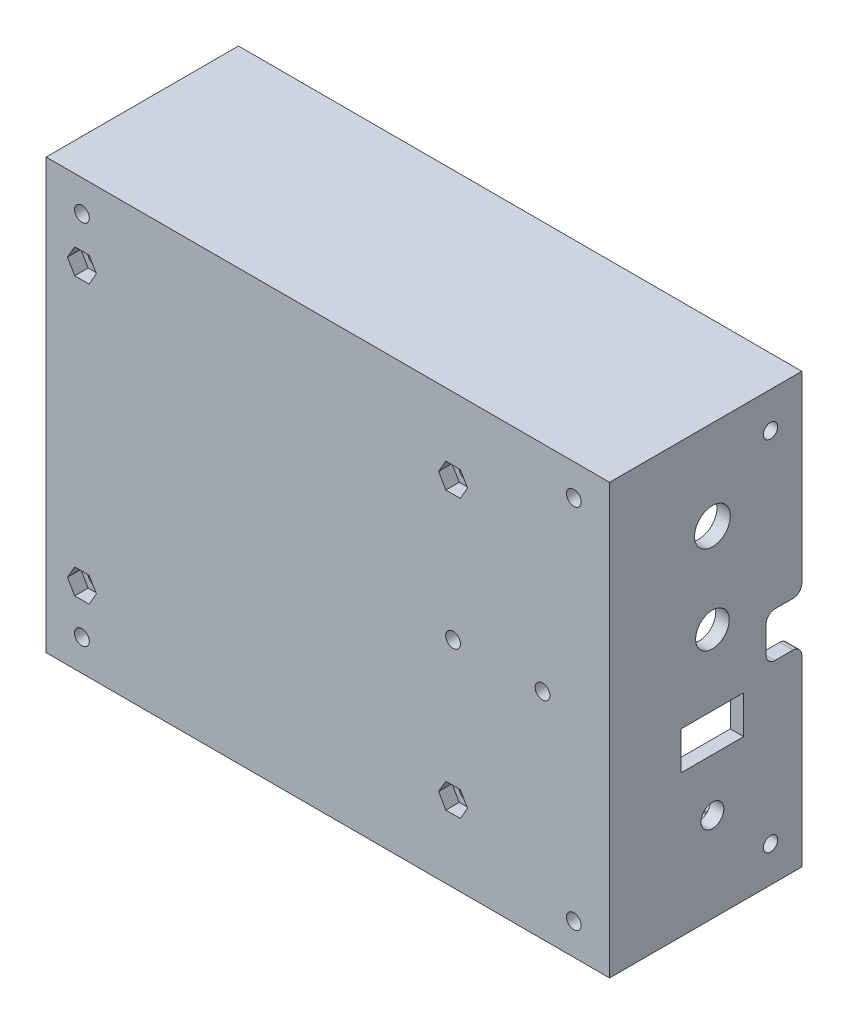
SolidWorks part; units mm, degrees
ref_plane "Front Plane" through (0, 0, 0) normal (0, 0, 1) x (1, 0, 0)
ref_plane "Top Plane" through (0, 0, 0) normal (0, 1, 0) x (1, 0, 0)
ref_plane "Right Plane" through (0, 0, 0) normal (1, 0, 0) x (0, 0, -1)
sketch "Sketch1" plane through (0, 0, 0) normal (0, 0, 1) x (1, 0, 0)
  line L1 (-60, -45) -> (60, -45)
  line L2 (-60, -45) -> (-60, 45)
  line L3 (-60, 45) -> (60, 45)
  line L4 (60, -45) -> (60, 45)
  line L5 (-60, -45) -> (60, 45) construction
  line L6 (-60, 45) -> (60, -45) construction
  line L7 (-55, -31) -> (28, -31)
  line L8 (-55, -31) -> (-55, 31)
  line L9 (-55, 31) -> (28, 31)
  line L10 (28, -31) -> (28, 31)
  line L11 (-55, -31) -> (28, 31) construction
  line L12 (-55, 31) -> (28, -31) construction
  circle A0 centre (-55, 31) radius 1.65
  circle A1 centre (28, 31) radius 1.65
  circle A2 centre (28, -31) radius 1.65
  circle A3 centre (-55, -31) radius 1.65
  circle A4 centre (-55, 41) radius 1.65
  circle A5 centre (55, 41) radius 1.65
  circle A6 centre (55, -41) radius 1.65
  circle A7 centre (-55, -41) radius 1.65
  point P0 (0, 0)
  point P6 (-13.5, 0)
  dimension "D7" = 3.3
  dimension "D8" = 4
  dimension "D9" = 5
  dimension "D10" = 5
  dimension "D11" = 4
  dimension "D12" = 3.3
  dimension "D13" = 5
  dimension "D14" = 4
  dimension "D15" = 4
  dimension "D16" = 5
  dimension "D1" = 90
  dimension "D2" = 120
  dimension "D3" = 62
  dimension "D4" = 83
  dimension "D5" = 14
  dimension "D6" = 5
extrude "Boss-Extrude2" add sketch "Sketch1" along normal blind 4 contours L1 L4 L3 L2 A3 L8 A0 L9 A1 L10 A2 L7 | A3 L7 A2 L10 A1 L9 A0 L8 region at (-58.5, 0, 0) region at (-13.5, 0, 0)
sketch "Sketch2" plane through (0, 0, 4) normal (0, 0, 1) x (1, 0, 0)
  line L1 (60, -45) -> (-60, -45)
  line L2 (60, -45) -> (60, 45)
  line L3 (60, 45) -> (-60, 45)
  line L4 (-60, -45) -> (-60, 45)
  line L5 (60, -45) -> (-60, 45) construction
  line L6 (60, 45) -> (-60, -45) construction
  line L7 (63, -48) -> (-63, -48)
  line L8 (63, -48) -> (63, 48)
  line L9 (63, 48) -> (-63, 48)
  line L10 (-63, -48) -> (-63, 48)
  line L11 (63, -48) -> (-63, 48) construction
  line L12 (63, 48) -> (-63, -48) construction
  point P0 (0, 0)
  point P7 (0, 0)
  dimension "D1" = 3
  dimension "D2" = 3
extrude "Boss-Extrude3" add sketch "Sketch2" against normal blind 43
sketch "Sketch3" plane through (-63, 0, 0) normal (-1, 0, 0) x (0, 0, 1)
  line L0 (-39, 48) -> (-39, -48) construction
  line L1 (-39, 48) -> (4, 48) construction
  line L2 (-39, -48) -> (4, -48) construction
  circle A0 centre (-32, -40) radius 1.6
  circle A1 centre (-32, 40) radius 1.6
  dimension "D1" = 3.2
  dimension "D2" = 7
  dimension "D3" = 8
  dimension "D4" = 8
  dimension "D5" = 7
  dimension "D6" = 3.2
extrude "Cut-Extrude1" cut sketch "Sketch3" against normal up to surface (126 mm away) up to face at (63, 0, -17.5)
sketch "Sketch4" plane through (63, 0, 0) normal (1, 0, 0) x (0, 0, -1)
  line L0 (39, -48) -> (39, 48) construction
  line L1 (39, 5) -> (31, 5)
  line L2 (39, 5) -> (39, -5)
  line L3 (39, -5) -> (31, -5)
  line L4 (31, 5) -> (31, -5)
  line L5 (39, -48) -> (-4, -48) construction
  line L6 (39, 48) -> (-4, 48) construction
  line L9 (12, -16.25) -> (26, -16.25)
  line L10 (12, -16.25) -> (12, -7.75)
  line L11 (12, -7.75) -> (26, -7.75)
  line L12 (26, -16.25) -> (26, -7.75)
  line L13 (12, -16.25) -> (26, -7.75) construction
  line L14 (12, -7.75) -> (26, -16.25) construction
  circle A1 centre (19, 8) radius 3.75
  point P8 (19, -12)
  dimension "D4" = 7.5
  dimension "D5" = 8.5
  dimension "D6" = 20
  dimension "D7" = 14
  dimension "D8" = 40
  dimension "D9" = 20
  dimension "D1" = 8
  dimension "D2" = 10
  dimension "D3" = 43
  dimension "D10" = 20
extrude "Cut-Extrude3" cut sketch "Sketch4" against normal blind 10
sketch "Sketch5" plane through (63, 0, 0) normal (1, 0, 0) x (0, 0, -1)
  line L0 (39, 5) -> (39, 48) construction
  line L1 (39, 48) -> (-4, 48) construction
  circle A0 centre (19, 28) radius 4
  dimension "D1" = 8
  dimension "D2" = 20
  dimension "D3" = 20
extrude "Cut-Extrude4" cut sketch "Sketch5" against normal blind 10
sketch "Sketch6" plane through (63, 0, 0) normal (1, 0, 0) x (0, 0, -1)
  line L0 (27, -28) -> (11, -28)
  line L1 (39, -48) -> (39, -5) construction
  line L3 (39, -48) -> (-4, -48) construction
  line L4 (-4, -48) -> (-4, 48) construction
  circle A0 centre (19, -28) radius 2.55
  point P3 (19, -28)
  dimension "D5" = 5.1
  dimension "D2" = 20
  dimension "D1" = 16
  dimension "D3" = 20
extrude "Cut-Extrude5" cut sketch "Sketch6" against normal blind 10 contours L0 A0 | A0 region at (63, -29.0823, -19)
sketch "Sketch8" plane through (0, 0, 0) normal (0, 0, -1) x (-1, 0, 0)
  line L0 (-60, 5) -> (-60, -5) construction
  circle A0 centre (-48, 0) radius 1.65
  circle A1 centre (-28, 0) radius 1.65
  circle A2 centre (-28, 31) radius 1.65 construction
  dimension "D1" = 3.3
  dimension "D2" = 3.3
  dimension "D3" = 20
  dimension "D4" = 31
  dimension "D5" = 31
  dimension "D6" = 12
extrude "Cut-Extrude6" cut sketch "Sketch8" against normal blind 10
sketch "Sketch9" plane through (0, 0, 0) normal (0, 0, -1) x (-1, 0, 0)
  line L0 (60, -45) -> (-60, -45) construction
  line L1 (-46.3834, 2.8) -> (-49.6166, 2.8)
  line L2 (-49.6166, 2.8) -> (-51.2332, 0)
  line L3 (-51.2332, 0) -> (-49.6166, -2.8)
  line L4 (-49.6166, -2.8) -> (-46.3834, -2.8)
  line L5 (-46.3834, -2.8) -> (-44.7668, 0)
  line L6 (-44.7668, 0) -> (-46.3834, 2.8)
  line L7 (-26.3834, 2.8) -> (-29.6166, 2.8)
  line L8 (-29.6166, 2.8) -> (-31.2332, 0)
  line L9 (-31.2332, 0) -> (-29.6166, -2.8)
  line L10 (-29.6166, -2.8) -> (-26.3834, -2.8)
  line L11 (-26.3834, -2.8) -> (-24.7668, 0)
  line L12 (-24.7668, 0) -> (-26.3834, 2.8)
  line L13 (-45.2287, 4.8) -> (-50.7713, 4.8)
  line L14 (-50.7713, 4.8) -> (-53.5426, 0)
  line L15 (-53.5426, 0) -> (-50.7713, -4.8)
  line L16 (-50.7713, -4.8) -> (-45.2287, -4.8)
  line L17 (-45.2287, -4.8) -> (-42.4574, 0)
  line L18 (-42.4574, 0) -> (-45.2287, 4.8)
  line L19 (-25.2287, 4.8) -> (-30.7713, 4.8)
  line L20 (-30.7713, 4.8) -> (-33.5426, 0)
  line L21 (-33.5426, 0) -> (-30.7713, -4.8)
  line L22 (-30.7713, -4.8) -> (-25.2287, -4.8)
  line L23 (-25.2287, -4.8) -> (-22.4574, 0)
  line L24 (-22.4574, 0) -> (-25.2287, 4.8)
  line L25 (60, -45) -> (-60, -45) construction
  line L26 (-51.7668, 41) -> (-53.3834, 43.8)
  line L27 (-53.3834, 43.8) -> (-56.6166, 43.8)
  line L28 (-56.6166, 43.8) -> (-58.2332, 41)
  line L29 (-58.2332, 41) -> (-56.6166, 38.2)
  line L30 (-56.6166, 38.2) -> (-53.3834, 38.2)
  line L31 (-53.3834, 38.2) -> (-51.7668, 41)
  line L32 (-50.6121, 41) -> (-52.8061, 44.8)
  line L33 (-52.8061, 44.8) -> (-57.1939, 44.8)
  line L34 (-57.1939, 44.8) -> (-59.3879, 41)
  line L35 (-59.3879, 41) -> (-57.1939, 37.2)
  line L36 (-57.1939, 37.2) -> (-52.8061, 37.2)
  line L37 (-52.8061, 37.2) -> (-50.6121, 41)
  line L38 (58.2332, 41) -> (56.6166, 43.8)
  line L39 (56.6166, 43.8) -> (53.3834, 43.8)
  line L40 (53.3834, 43.8) -> (51.7668, 41)
  line L41 (51.7668, 41) -> (53.3834, 38.2)
  line L42 (53.3834, 38.2) -> (56.6166, 38.2)
  line L43 (56.6166, 38.2) -> (58.2332, 41)
  line L44 (52.8061, 44.8) -> (50.6121, 41)
  line L45 (50.6121, 41) -> (52.8061, 37.2)
  line L46 (52.8061, 37.2) -> (57.1939, 37.2)
  line L47 (57.1939, 37.2) -> (59.3879, 41)
  line L48 (59.3879, 41) -> (57.1939, 44.8)
  line L49 (57.1939, 44.8) -> (52.8061, 44.8)
  line L50 (53.3834, -38.2) -> (51.7668, -41)
  line L51 (51.7668, -41) -> (53.3834, -43.8)
  line L52 (53.3834, -43.8) -> (56.6166, -43.8)
  line L53 (56.6166, -43.8) -> (58.2332, -41)
  line L54 (58.2332, -41) -> (56.6166, -38.2)
  line L55 (56.6166, -38.2) -> (53.3834, -38.2)
  line L56 (50.6121, -41) -> (52.8061, -44.8)
  line L57 (52.8061, -44.8) -> (57.1939, -44.8)
  line L58 (57.1939, -44.8) -> (59.3879, -41)
  line L59 (59.3879, -41) -> (57.1939, -37.2)
  line L60 (57.1939, -37.2) -> (52.8061, -37.2)
  line L61 (52.8061, -37.2) -> (50.6121, -41)
  line L62 (-53.3834, -38.2) -> (-56.6166, -38.2)
  line L63 (-56.6166, -38.2) -> (-58.2332, -41)
  line L64 (-58.2332, -41) -> (-56.6166, -43.8)
  line L65 (-56.6166, -43.8) -> (-53.3834, -43.8)
  line L66 (-53.3834, -43.8) -> (-51.7668, -41)
  line L67 (-51.7668, -41) -> (-53.3834, -38.2)
  line L68 (-52.8061, -37.2) -> (-57.1939, -37.2)
  line L69 (-57.1939, -37.2) -> (-59.3879, -41)
  line L70 (-59.3879, -41) -> (-57.1939, -44.8)
  line L71 (-57.1939, -44.8) -> (-52.8061, -44.8)
  line L72 (-52.8061, -44.8) -> (-50.6121, -41)
  line L73 (-50.6121, -41) -> (-52.8061, -37.2)
  circle A0 centre (-48, 0) radius 2.8 construction
  circle A1 centre (-28, 0) radius 2.8 construction
  circle A2 centre (-48, 0) radius 4.8 construction
  circle A3 centre (-28, 0) radius 4.8 construction
  circle A4 centre (-55, 41) radius 2.8 construction
  circle A5 centre (-55, 41) radius 3.8 construction
  circle A6 centre (55, 41) radius 2.8 construction
  circle A7 centre (55, 41) radius 3.8 construction
  circle A8 centre (55, -41) radius 2.8 construction
  circle A9 centre (55, -41) radius 3.8 construction
  circle A10 centre (-55, -41) radius 2.8 construction
  circle A11 centre (-55, -41) radius 3.8 construction
  dimension "D1" = 5.6
  dimension "D2" = 2
  dimension "D3" = 5.6
  dimension "D4" = 1
extrude "Boss-Extrude4" add sketch "Sketch9" along normal blind 3
sketch "Sketch10" plane through (0, 0, 4) normal (0, 0, 1) x (1, 0, 0)
  line L0 (63, 48) -> (-63, 48) construction
  line L1 (-51.7668, 31) -> (-53.3834, 33.8)
  line L2 (-53.3834, 33.8) -> (-56.6166, 33.8)
  line L3 (-56.6166, 33.8) -> (-58.2332, 31)
  line L4 (-58.2332, 31) -> (-56.6166, 28.2)
  line L5 (-56.6166, 28.2) -> (-53.3834, 28.2)
  line L6 (-53.3834, 28.2) -> (-51.7668, 31)
  line L7 (31.2332, 31) -> (29.6166, 33.8)
  line L8 (29.6166, 33.8) -> (26.3834, 33.8)
  line L9 (26.3834, 33.8) -> (24.7668, 31)
  line L10 (24.7668, 31) -> (26.3834, 28.2)
  line L11 (26.3834, 28.2) -> (29.6166, 28.2)
  line L12 (29.6166, 28.2) -> (31.2332, 31)
  line L25 (-51.7668, -31) -> (-53.3834, -28.2)
  line L26 (-53.3834, -28.2) -> (-56.6166, -28.2)
  line L27 (-56.6166, -28.2) -> (-58.2332, -31)
  line L28 (-58.2332, -31) -> (-56.6166, -33.8)
  line L29 (-56.6166, -33.8) -> (-53.3834, -33.8)
  line L30 (-53.3834, -33.8) -> (-51.7668, -31)
  line L31 (31.2332, -31) -> (29.6166, -28.2)
  line L32 (29.6166, -28.2) -> (26.3834, -28.2)
  line L33 (26.3834, -28.2) -> (24.7668, -31)
  line L34 (24.7668, -31) -> (26.3834, -33.8)
  line L35 (26.3834, -33.8) -> (29.6166, -33.8)
  line L36 (29.6166, -33.8) -> (31.2332, -31)
  circle A0 centre (-55, 31) radius 2.8 construction
  circle A1 centre (28, 31) radius 2.8 construction
  circle A4 centre (-55, -31) radius 2.8 construction
  circle A5 centre (28, -31) radius 2.8 construction
  dimension "D2" = 5.6
fillet "Fillet1" radius 2 4 edges at (61.5, 5, -31) (61.5, -5, -31) (61.5, -5, -39) (61.5, 5, -39)
extrude "Cut-Extrude8" cut sketch "Sketch10" against normal blind 3
sketch "Sketch12" plane through (0, 0, 0) normal (0, 0, -1) x (-1, 0, 0)
  circle A0 centre (-28, 31) radius 1.65
  circle A1 centre (55, 31) radius 1.65
  circle A2 centre (55, -31) radius 1.65
  circle A3 centre (-28, -31) radius 1.65
  circle A4 centre (-28, -31) radius 3.5
  circle A5 centre (55, -31) radius 3.5
  circle A6 centre (55, 31) radius 3.5
  circle A7 centre (-28, 31) radius 3.5
  dimension "D1" = 7
extrude "Boss-Extrude11" add sketch "Sketch12" along normal blind 5
sketch "Sketch13" plane through (60, 0, 0) normal (-1, 0, 0) x (0, 0, 1)
  line L1 (-25, 22) -> (-13, 22)
  line L2 (-25, 22) -> (-25, 34)
  line L3 (-25, 34) -> (-13, 34)
  line L4 (-13, 22) -> (-13, 34)
  line L5 (-25, 22) -> (-13, 34) construction
  line L6 (-25, 34) -> (-13, 22) construction
  line L7 (-28, 20) -> (-10, 20)
  line L8 (-28, 20) -> (-28, 36)
  line L9 (-28, 36) -> (-10, 36)
  line L10 (-10, 20) -> (-10, 36)
  line L11 (-28, 20) -> (-10, 36) construction
  line L12 (-28, 36) -> (-10, 20) construction
  point P0 (-19, 28)
  point P6 (-19, 28)
  dimension "D1" = 12
  dimension "D2" = 12
  dimension "D3" = 2
  dimension "D4" = 3
extrude "Boss-Extrude12" add sketch "Sketch13" along normal blind 1
chamfer "Chamfer1" distance 1 angle 45 2 edges at (59, 28, -10) (59, 28, -28)
sketch "Sketch16" plane through (0, 0, 0) normal (0, 0, -1) x (-1, 0, 0)
  line L0 (-50.6121, 42) -> (51.5, 42)
  line L1 (51.5, 42) -> (51.5, 30.75)
  line L2 (54.75, 27.5) -> (57, 27.5)
  line L3 (57, 27.5) -> (57, -27.5)
  line L4 (57, -27.5) -> (54.75, -27.5)
  line L5 (51.5, -30.75) -> (51.5, -42)
  line L6 (51.5, -42) -> (-50.6121, -42)
  line L7 (-50.6121, -42) -> (-50.6121, -37.2)
  line L8 (-50.6121, -37.2) -> (-57, -37.2)
  line L9 (-57, -37.2) -> (-57, 37.2)
  line L10 (-57, 37.2) -> (-50.6121, 37.2)
  line L11 (-50.6121, 37.2) -> (-50.6121, 42)
  line L12 (-57, 4.8) -> (-22.4574, 4.8)
  line L13 (-22.4574, 4.8) -> (-22.4574, -4.8)
  line L14 (-22.4574, -4.8) -> (-57, -4.8)
  line L15 (-22.4574, 1.5) -> (57, 1.5)
  line L16 (57, 1.5) -> (57, -1.5)
  line L17 (57, -1.5) -> (-22.4574, -1.5)
  line L18 (-60, 45) -> (-60, -45)
  line L19 (60, -45) -> (-60, -45) construction
  line L20 (-60, -45) -> (-60, 45) construction
  line L21 (-60, -45) -> (60, -45)
  line L22 (60, -45) -> (60, 45)
  line L23 (60, 45) -> (-60, 45)
  line L24 (-1.5, 42) -> (-1.5, -42)
  line L25 (-1.5, -42) -> (1.5, -42)
  line L26 (1.5, -42) -> (1.5, 42)
  line L27 (1.5, 42) -> (-1.5, 42)
  line L28 (-45.2287, 4.8) -> (-50.7713, 4.8) construction
  line L29 (-50.7713, -4.8) -> (-45.2287, -4.8) construction
  line L30 (-60, 7) -> (-60, 45) construction
  line L31 (-52.8061, -37.2) -> (-57.1939, -37.2) construction
  line L32 (-57.1939, 37.2) -> (-52.8061, 37.2) construction
  line L33 (-50.6121, 41) -> (-52.8061, 37.2)
  line L34 (-52.8061, -37.2) -> (-50.6121, -41)
  line L35 (-22.4574, -1.5) -> (-24.3627, -4.8)
  line L36 (-24.3627, 4.8) -> (-22.4574, 1.5)
  line L37 (-22.4574, 0) -> (-25.2287, 4.8) construction
  line L38 (-25.2287, -4.8) -> (-22.4574, 0) construction
  circle A0 centre (55, -31) radius 3.5 construction
  circle A1 centre (55, 31) radius 3.5 construction
  arc A2 (54.75, -27.5) -> (51.5, -30.75) centre (54.75, -30.75) ccw
  arc A3 (51.5, 30.75) -> (54.75, 27.5) centre (54.75, 30.75) ccw
  point P60 (0, 0)
  circle M27 centre (-28, -31) radius 3.5
  line M34 (-45.2287, -4.8) -> (-50.7713, -4.8)
  line M37 (-50.7713, 4.8) -> (-45.2287, 4.8)
  line M40 (-25.2287, -4.8) -> (-30.7713, -4.8)
  line M43 (-30.7713, 4.8) -> (-25.2287, 4.8)
  line M44 (-50.6121, 41) -> (-52.8061, 37.2)
  line M45 (-52.8061, 37.2) -> (-57.1939, 37.2)
  line M54 (52.8061, 37.2) -> (50.6121, 41)
  line M55 (50.6121, 41) -> (52.8061, 44.8)
  line M56 (50.6121, -41) -> (52.8061, -37.2)
  line M61 (52.8061, -44.8) -> (50.6121, -41)
  line M62 (-52.8061, -37.2) -> (-50.6121, -41)
  line M67 (-57.1939, -37.2) -> (-52.8061, -37.2)
  circle M69 centre (-28, 31) radius 3.5
  dimension "D9" = 3.25
  dimension "D1" = 3
  dimension "D2" = 3
  dimension "D3" = 3
  dimension "D4" = 1.5
  dimension "D5" = 1.5
  dimension "D6" = 3
  dimension "D7" = 3
  dimension "D8" = 3
extrude "Cut-Extrude11" cut sketch "Sketch16" against normal blind 3 contours L24 L0 L11 L10 L9 L12 L13 L15 M45 M37 M43 M69 | L26 L15 L3 L2 L1 L0 M54 M55 | L26 L6 L5 L4 L3 L17 M61 M56 | L24 L17 L13 L14 L9 L8 L7 L6 M40 M34 M67 M27 | L7 L8 M62 | L10 L11 M44 | L12 L36 L13 | L13 L35 L14 region at (28.3301, 22.3394, 0) region at (51.3434, 38.4667, 0) region at (-28.3418, 21.2674, 0) region at (23.0925, 3.7, 0) region at (28.3301, -22.3394, 0) region at (-28.3418, -21.2674, 0) region at (23.0925, -3.7, 0) region at (51.3434, -38.4667, 0)
sketch "Sketch17" plane through (0, 45, 0) normal (0, -1, 0) x (1, 0, 0)
  line L1 (-57, -36) -> (57, -36)
  line L2 (-57, -36) -> (-57, -3)
  line L3 (-57, -3) -> (57, -3)
  line L4 (57, -36) -> (57, -3)
  line L5 (-60, 0) -> (60, 0) construction
  line L6 (60, -39) -> (60, 0) construction
  line L7 (-60, -39) -> (-60, 0) construction
  line L8 (60, -39) -> (-60, -39) construction
  line L9 (-1.5, 3) -> (-1.5, 0) construction
  line L10 (-57, -18) -> (57, -18)
  line L11 (-57, -18) -> (-57, -21)
  line L12 (-57, -21) -> (57, -21)
  line L13 (57, -18) -> (57, -21)
  line L14 (-1.5, -3) -> (1.5, -3)
  line L15 (-1.5, -3) -> (-1.5, -36)
  line L16 (-1.5, -36) -> (1.5, -36)
  line L17 (1.5, -3) -> (1.5, -36)
  dimension "D1" = 3
  dimension "D2" = 3
  dimension "D3" = 3
  dimension "D4" = 3
  dimension "D5" = 3
  dimension "D6" = 3
  dimension "D7" = 15
extrude "Cut-Extrude13" cut sketch "Sketch17" against normal blind 2 contours L15 L12 L2 L1 | L15 L3 L2 L10 | L3 L17 L10 L4 | L12 L17 L1 L4 region at (-29.25, 45, -28.5) region at (29.25, 45, -28.5) region at (-29.25, 45, -10.5) region at (29.25, 45, -10.5)
sketch "Sketch20" plane through (0, -45, 0) normal (0, 1, 0) x (1, 0, 0)
  line L0 (-57, -3) -> (-57, 0) construction
  line L1 (-57, 36) -> (57, 36)
  line L2 (-57, 36) -> (-57, 3)
  line L3 (-57, 3) -> (57, 3)
  line L4 (57, 36) -> (57, 3)
  line L5 (-1.5, 36) -> (1.5, 36)
  line L6 (-1.5, 36) -> (-1.5, 3)
  line L7 (-1.5, 3) -> (1.5, 3)
  line L8 (1.5, 36) -> (1.5, 3)
  line L9 (-57, 21) -> (57, 21)
  line L10 (-57, 21) -> (-57, 18)
  line L11 (-57, 18) -> (57, 18)
  line L12 (57, 21) -> (57, 18)
  line L13 (57, -3) -> (57, 0) construction
  line L14 (1.5, 36) -> (57, 36) construction
  line L16 (-57, 21) -> (-1.5, 21) construction
  line L17 (-57, 3) -> (-1.5, 3) construction
  line L18 (1.5, 21) -> (57, 21) construction
  line L19 (-57, 18) -> (-1.5, 18) construction
  line L20 (-1.5, 3) -> (-1.5, 18) construction
  line L21 (1.5, 3) -> (1.5, 18) construction
  point P20 (0, 0)
  point P21 (0, 0)
  point P22 (0, 0)
  point P23 (0, 0)
  point P24 (0, 0)
  point P25 (0, 0)
extrude "Cut-Extrude14" cut sketch "Sketch20" against normal blind 2 contours L2 L9 L6 L1 | L8 L9 L4 L1 | L11 L8 L3 L4 | L11 L2 L3 L6 region at (-29.25, -45, -28.5) region at (29.25, -45, -28.5) region at (-29.25, -45, -10.5) region at (29.25, -45, -10.5)
sketch "Sketch21" plane through (-60, 0, 0) normal (1, 0, 0) x (0, 0, -1)
  line L0 (0, -45) -> (0, 45) construction
  line L1 (28, 42) -> (3, 42)
  line L2 (28, 42) -> (28, -42)
  line L3 (28, -42) -> (3, -42)
  line L4 (3, 42) -> (3, -42)
  line L5 (28, 36) -> (36, 36)
  line L6 (28, 36) -> (28, -36)
  line L7 (28, -36) -> (36, -36)
  line L8 (36, 36) -> (36, -36)
  line L9 (3, 1.5) -> (36, 1.5)
  line L10 (3, 1.5) -> (3, -1.5)
  line L11 (3, -1.5) -> (36, -1.5)
  line L12 (36, 1.5) -> (36, -1.5)
  line L13 (21, 42) -> (18, 42)
  line L14 (21, 42) -> (21, -42)
  line L15 (21, -42) -> (18, -42)
  line L16 (18, 42) -> (18, -42)
  line L17 (39, 45) -> (0, 45) construction
  line L18 (39, 45) -> (39, -45) construction
  line L19 (39, -45) -> (0, -45) construction
  line L20 (-3, -1.5) -> (0, -1.5) construction
  point P26 (0, 0)
  point P27 (0, 0)
  point P28 (0, 0)
  point P29 (18.6772, 38.1454)
  dimension "D1" = 3
  dimension "D2" = 3
  dimension "D3" = 3
  dimension "D4" = 3
  dimension "D5" = 6
  dimension "D6" = 6
  dimension "D7" = 8
  dimension "D8" = 3
  dimension "D9" = 3
  dimension "D10" = 15
extrude "Cut-Extrude15" cut sketch "Sketch21" against normal blind 2 contours L2 L9 L8 L5 | L1 L14 L9 L2 | L11 L2 L7 L8 | L11 L14 L3 L2 | L16 L11 L4 L3 | L16 L1 L4 L9 region at (-60, 21.75, -24.5) region at (-60, 18.75, -32) region at (-60, 21.75, -10.5) region at (-60, -21.75, -24.5) region at (-60, -18.75, -32) region at (-60, -21.75, -10.5)
chamfer "Chamfer6" distance 1.5 angle 45 14 edges at (29.25, -47, -18) (29.25, -47, -36) (-29.25, -47, -36) (-29.25, -47, -18) (-62, 21.75, -18) (-62, -21.75, -18) (-62, 39, -28) (-62, -18.75, -36) (-62, -39, -28) (-62, 18.75, -36) (-29.25, 47, -18) (29.25, 47, -18) (-29.25, 47, -36) (29.25, 47, -36)
